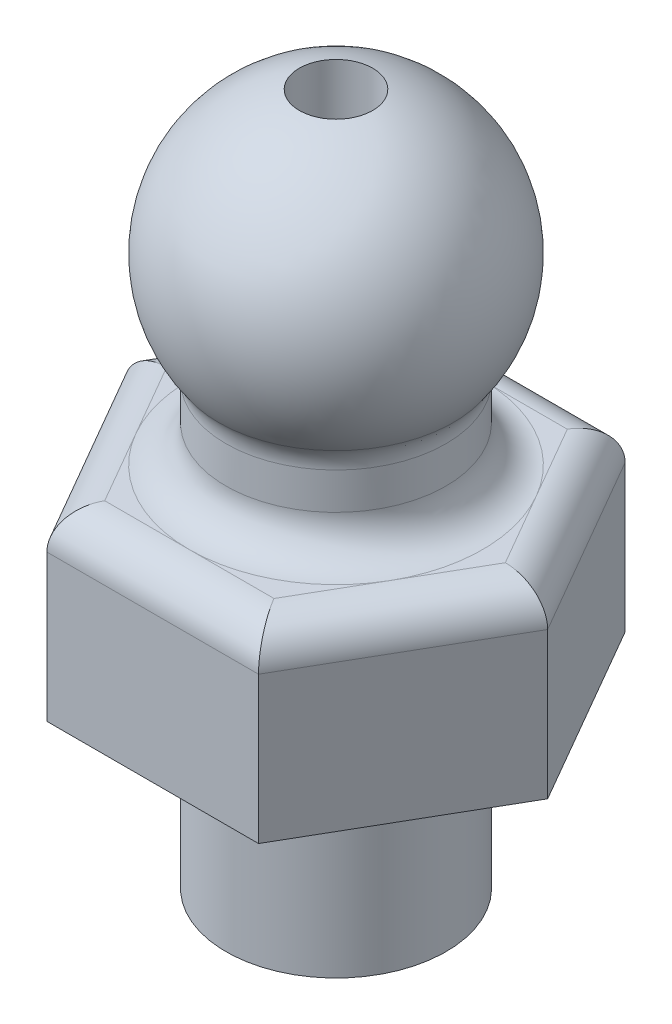
SolidWorks part; units mm, degrees
ref_plane "Front Plane" through (0, 0, 0) normal (0, 0, 1) x (1, 0, 0)
ref_plane "Top Plane" through (0, 0, 0) normal (0, 1, 0) x (1, 0, 0)
ref_plane "Right Plane" through (0, 0, 0) normal (1, 0, 0) x (0, 0, -1)
sketch "Sketch1" plane through (0, 0, 0) normal (0, 0, 1) x (1, 0, 0)
  line L0 (-1, 0) -> (-3, 0)
  line L1 (-3, 0) -> (-3, 5)
  line L2 (-3, 5) -> (-6, 5)
  line L3 (-6, 5) -> (-6, 10)
  line L4 (-6, 10) -> (-3, 10)
  line L5 (-3, 10) -> (-3, 12.3542)
  line L6 (0, 0) -> (0, 23.9548) construction
  line L7 (-2, 15) -> (-2, 7)
  line L8 (-2, 7) -> (-1, 7)
  line L9 (-1, 7) -> (-1, 0)
  line L10 (-1, 16.7321) -> (-1, 18.873)
  arc A0 (-1, 18.873) -> (-3, 12.3542) centre (0, 15) ccw
  arc A1 (-1, 16.7321) -> (-2, 15) centre (0, 15) ccw
  dimension "D5" = 8
  dimension "D1" = 3
  dimension "D2" = 5
  dimension "D3" = 3
  dimension "D4" = 5
  dimension "D6" = 15
  dimension "D7" = 2
  dimension "D8" = 4
  dimension "D9" = 7
revolve "Revolve1" add sketch "Sketch1" angle 360 about L6
sketch "Sketch2" plane through (0, 10, 0) normal (0, 1, 0) x (1, 0, 0)
  line L1 (5.7735, 0) -> (2.8868, 5)
  line L2 (2.8868, 5) -> (-2.8868, 5)
  line L3 (-2.8868, 5) -> (-5.7735, 0)
  line L4 (-5.7735, 0) -> (-2.8868, -5)
  line L5 (-2.8868, -5) -> (2.8868, -5)
  line L6 (2.8868, -5) -> (5.7735, 0)
  circle A0 centre (0, 0) radius 5 construction
  circle A1 centre (0, 0) radius 10.0681
  dimension "D1" = 10
extrude "Cut-Extrude1" cut sketch "Sketch2" against normal blind 10
fillet "Fillet1" radius 1 2 edges at (0, 12.3542, -3) (0, 10, -3)
fillet "Fillet2" radius 1 6 edges at (0, 10, 5) (-4.3301, 10, 2.5) (-4.3301, 10, -2.5) (0, 10, -5) (4.3301, 10, -2.5) (4.3301, 10, 2.5)
sketch "Sketch3" plane through (0, 10, 0) normal (0, 1, 0) x (1, 0, 0)
  line L1 (-0.5, 2.3) -> (0.5, 2.3)
  line L2 (-0.5, 2.3) -> (-0.5, 1.3635)
  line L3 (-0.5, 1.3635) -> (0.5, 1.3635)
  line L4 (0.5, 2.3) -> (0.5, 1.3635)
  dimension "D1" = 2.3
  dimension "D2" = 1
  dimension "D3" = 0.5
extrude "Cut-Extrude2" cut sketch "Sketch3" against normal up to surface (3 mm away) up to face at (0, 7, -2)
pattern_circular "CirPattern1" count 6 over 360 about axis through (0, 0, 0) along (0, -1, 0) of "Cut-Extrude2"
